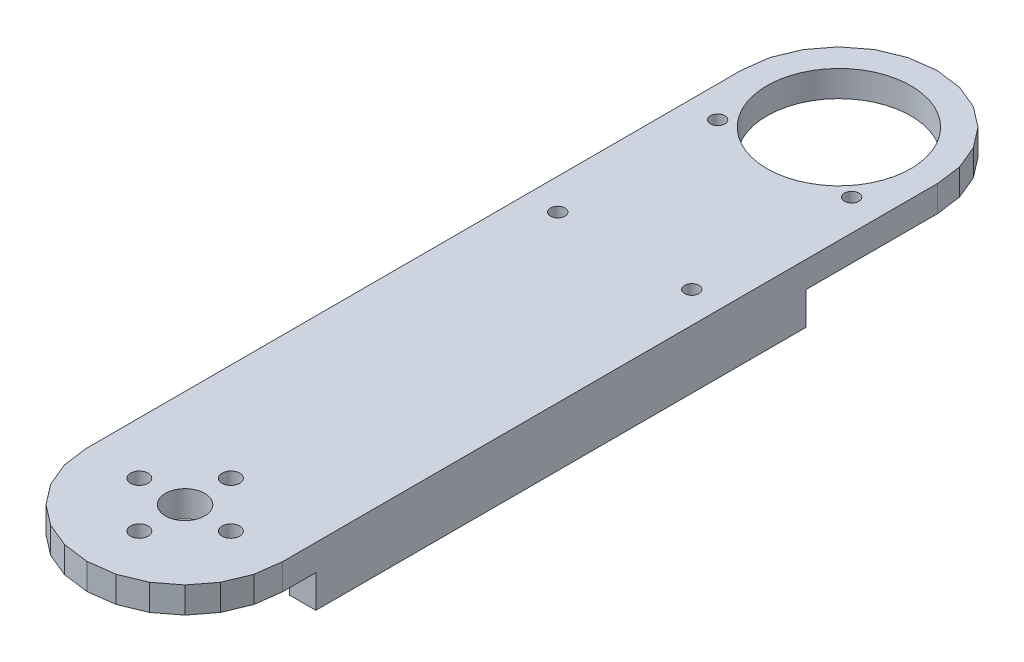
SolidWorks part; units mm, degrees
ref_plane "Front Plane" through (0, 0, 0) normal (0, 0, 1) x (1, 0, 0)
ref_plane "Top Plane" through (0, 0, 0) normal (0, 1, 0) x (1, 0, 0)
ref_plane "Right Plane" through (0, 0, 0) normal (1, 0, 0) x (0, 0, -1)
ref_plane "PY_m22_625" through (0, -22.625, 0) normal (0, 1, 0) x (1, 0, 0)
sketch "S_prism1" plane through (0, -22.625, 0) normal (0, 1, 0) x (1, 0, 0)
  line L0 (-15, -0.1) -> (-14.492, -3.956)
  line L1 (-14.492, -3.956) -> (-13.004, -7.55)
  line L2 (-13.004, -7.55) -> (-10.636, -10.636)
  line L3 (-10.636, -10.636) -> (-7.55, -13.004)
  line L4 (-7.55, -13.004) -> (-3.956, -14.492)
  line L5 (-3.956, -14.492) -> (-0.1, -15)
  line L6 (-0.1, -15) -> (0.1, -15)
  line L7 (0.1, -15) -> (3.956, -14.492)
  line L8 (3.956, -14.492) -> (7.55, -13.004)
  line L9 (7.55, -13.004) -> (10.636, -10.636)
  line L10 (10.636, -10.636) -> (13.004, -7.55)
  line L11 (13.004, -7.55) -> (14.492, -3.956)
  line L12 (14.492, -3.956) -> (15, -0.1)
  line L13 (15, -0.1) -> (15, 100.1)
  line L14 (15, 100.1) -> (14.492, 103.956)
  line L15 (14.492, 103.956) -> (13.004, 107.55)
  line L16 (13.004, 107.55) -> (10.636, 110.636)
  line L17 (10.636, 110.636) -> (7.55, 113.004)
  line L18 (7.55, 113.004) -> (3.956, 114.492)
  line L19 (3.956, 114.492) -> (0.1, 115)
  line L20 (0.1, 115) -> (-0.1, 115)
  line L21 (-0.1, 115) -> (-3.956, 114.492)
  line L22 (-3.956, 114.492) -> (-7.55, 113.004)
  line L23 (-7.55, 113.004) -> (-10.636, 110.636)
  line L24 (-10.636, 110.636) -> (-13.004, 107.55)
  line L25 (-13.004, 107.55) -> (-14.492, 103.956)
  line L26 (-14.492, 103.956) -> (-15, 100.1)
  line L27 (-15, 100.1) -> (-15, -0.1)
  dimension "P1" = 15
  dimension "P2" = 0.1
  dimension "P3" = 14.492
  dimension "P4" = 3.956
  dimension "P5" = 13.004
  dimension "P6" = 7.55
  dimension "P7" = 10.636
  dimension "P8" = 10.636
  dimension "P9" = 7.55
  dimension "P10" = 13.004
  dimension "P11" = 3.956
  dimension "P12" = 14.492
  dimension "P13" = 0.1
  dimension "P14" = 15
  dimension "P15" = 0.1
  dimension "P16" = 15
  dimension "P17" = 3.956
  dimension "P18" = 14.492
  dimension "P19" = 7.55
  dimension "P20" = 13.004
  dimension "P21" = 10.636
  dimension "P22" = 10.636
  dimension "P23" = 13.004
  dimension "P24" = 7.55
  dimension "P25" = 14.492
  dimension "P26" = 3.956
  dimension "P27" = 15
  dimension "P28" = 0.1
  dimension "P29" = 15
  dimension "P30" = 100.1
  dimension "P31" = 14.492
  dimension "P32" = 103.956
  dimension "P33" = 13.004
  dimension "P34" = 107.55
  dimension "P35" = 10.636
  dimension "P36" = 110.636
  dimension "P37" = 7.55
  dimension "P38" = 113.004
  dimension "P39" = 3.956
  dimension "P40" = 114.492
  dimension "P41" = 0.1
  dimension "P42" = 115
  dimension "P43" = 0.1
  dimension "P44" = 115
  dimension "P45" = 3.956
  dimension "P46" = 114.492
  dimension "P47" = 7.55
  dimension "P48" = 113.004
  dimension "P49" = 10.636
  dimension "P50" = 110.636
  dimension "P51" = 13.004
  dimension "P52" = 107.55
  dimension "P53" = 14.492
  dimension "P54" = 103.956
  dimension "P55" = 15
  dimension "P56" = 100.1
extrude "Boss_1" add sketch "S_prism1" along normal blind 4
ref_plane "PZ_m80_000" through (0, 0, -80) normal (0, 0, 1) x (1, 0, 0)
sketch "S_box2" plane through (0, 0, -80) normal (0, 0, 1) x (1, 0, 0)
  line L0 (-15, -27.625) -> (-11, -27.625)
  line L1 (-11, -27.625) -> (-11, -22.125)
  line L2 (-11, -22.125) -> (-15, -22.125)
  line L3 (-15, -22.125) -> (-15, -27.625)
  dimension "P1" = 15
  dimension "P2" = 27.625
  dimension "P3" = 11
  dimension "P4" = 27.625
  dimension "P5" = 11
  dimension "P6" = 22.125
  dimension "P7" = 15
  dimension "P8" = 22.125
extrude "Boss_2" add sketch "S_box2" along normal blind 75
sketch "S_box3" plane through (0, 0, -80) normal (0, 0, 1) x (1, 0, 0)
  line L0 (11, -27.625) -> (15, -27.625)
  line L1 (15, -27.625) -> (15, -22.125)
  line L2 (15, -22.125) -> (11, -22.125)
  line L3 (11, -22.125) -> (11, -27.625)
  dimension "P1" = 11
  dimension "P2" = 27.625
  dimension "P3" = 15
  dimension "P4" = 27.625
  dimension "P5" = 15
  dimension "P6" = 22.125
  dimension "P7" = 11
  dimension "P8" = 22.125
extrude "Boss_3" add sketch "S_box3" along normal blind 75
ref_plane "PY_m22_725" through (0, -22.725, 0) normal (0, 1, 0) x (1, 0, 0)
sketch "S_hole4" plane through (0, -22.725, 0) normal (0, 1, 0) x (1, 0, 0)
  circle A0 centre (0, 0) radius 3
  dimension "D1_S_hole4" = 6
extrude "Hole_4" cut sketch "S_hole4" along normal blind 4.2
sketch "S_hole5" plane through (0, -22.725, 0) normal (0, 1, 0) x (1, 0, 0)
  circle A0 centre (7, 0) radius 1.35
  dimension "D1_S_hole5" = 2.7
  dimension "P2" = 7
extrude "Hole_5" cut sketch "S_hole5" along normal blind 4.2
sketch "S_hole6" plane through (0, -22.725, 0) normal (0, 1, 0) x (1, 0, 0)
  circle A0 centre (0, -7) radius 1.35
  dimension "D1_S_hole6" = 2.7
  dimension "P2" = 7
extrude "Hole_6" cut sketch "S_hole6" along normal blind 4.2
sketch "S_hole7" plane through (0, -22.725, 0) normal (0, 1, 0) x (1, 0, 0)
  circle A0 centre (-7, 0) radius 1.35
  dimension "D1_S_hole7" = 2.7
  dimension "P2" = 7
extrude "Hole_7" cut sketch "S_hole7" along normal blind 4.2
sketch "S_hole8" plane through (0, -22.725, 0) normal (0, 1, 0) x (1, 0, 0)
  circle A0 centre (0, 7) radius 1.35
  dimension "D1_S_hole8" = 2.7
  dimension "P2" = 7
extrude "Hole_8" cut sketch "S_hole8" along normal blind 4.2
sketch "S_hole9" plane through (0, -22.725, 0) normal (0, 1, 0) x (1, 0, 0)
  circle A0 centre (0, 100) radius 11
  dimension "D1_S_hole9" = 22
  dimension "P2" = 100
extrude "Hole_9" cut sketch "S_hole9" along normal blind 4.2
sketch "S_hole10" plane through (0, -22.725, 0) normal (0, 1, 0) x (1, 0, 0)
  circle A0 centre (-10.25, 91.7) radius 1.1
  dimension "D1_S_hole10" = 2.2
  dimension "P2" = 10.25
  dimension "P3" = 91.7
extrude "Hole_10" cut sketch "S_hole10" along normal blind 4.2
sketch "S_hole11" plane through (0, -22.725, 0) normal (0, 1, 0) x (1, 0, 0)
  circle A0 centre (10.25, 91.7) radius 1.1
  dimension "D1_S_hole11" = 2.2
  dimension "P2" = 10.25
  dimension "P3" = 91.7
extrude "Hole_11" cut sketch "S_hole11" along normal blind 4.2
sketch "S_hole12" plane through (0, -22.725, 0) normal (0, 1, 0) x (1, 0, 0)
  circle A0 centre (-10.25, 67.25) radius 1.1
  dimension "D1_S_hole12" = 2.2
  dimension "P2" = 10.25
  dimension "P3" = 67.25
extrude "Hole_12" cut sketch "S_hole12" along normal blind 4.2
sketch "S_hole13" plane through (0, -22.725, 0) normal (0, 1, 0) x (1, 0, 0)
  circle A0 centre (10.25, 67.25) radius 1.1
  dimension "D1_S_hole13" = 2.2
  dimension "P2" = 10.25
  dimension "P3" = 67.25
extrude "Hole_13" cut sketch "S_hole13" along normal blind 4.2
equation "\"plate_t\" = 3"
equation "\"clearance\" = 0.4"
